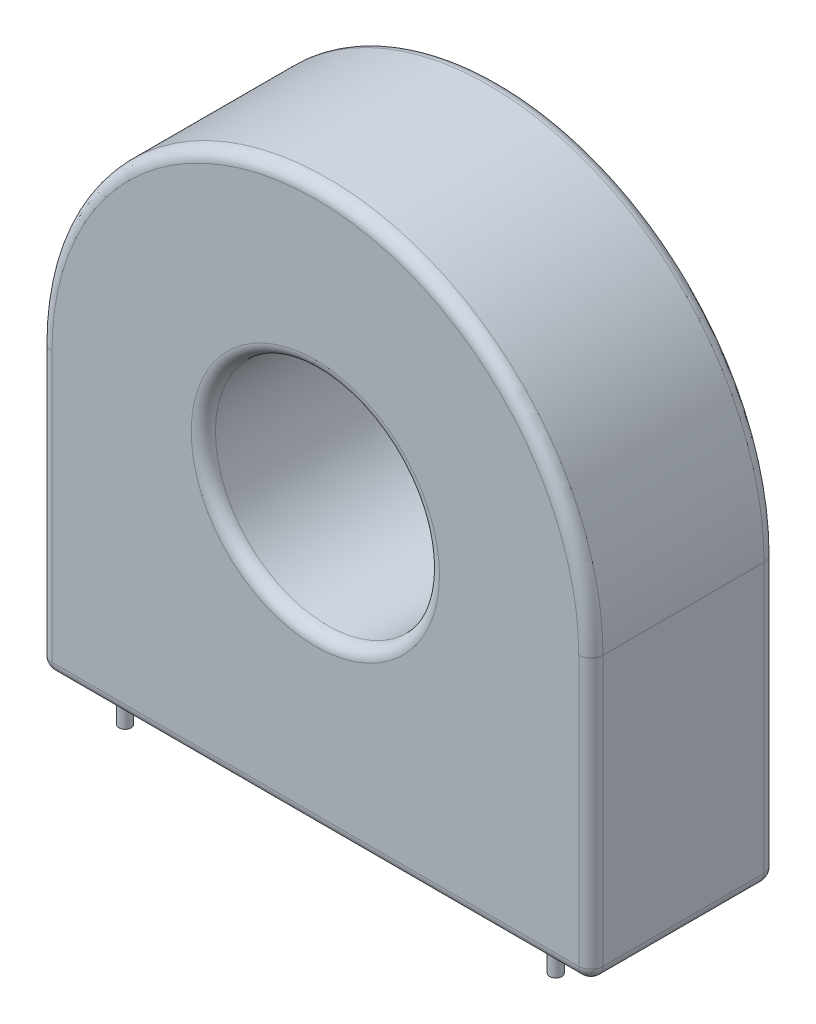
SolidWorks part; units mm, degrees
ref_plane "Front Plane" through (0, 0, 0) normal (0, 0, 1) x (1, 0, 0)
ref_plane "Top Plane" through (0, 0, 0) normal (0, 1, 0) x (1, 0, 0)
ref_plane "Right Plane" through (0, 0, 0) normal (1, 0, 0) x (0, 0, -1)
sketch "Sketch1" plane through (0, 0, 0) normal (0, 0, 1) x (1, 0, 0)
  line L0 (0, 56.047) -> (0, -94.9477) construction
  line L1 (0, 34.375) -> (50.579, 34.375) construction
  line L2 (-22.75, 11.625) -> (22.75, 11.625) construction
  line L3 (-22.75, 11.625) -> (-22.75, -11.625)
  line L4 (-22.75, -11.625) -> (22.75, -11.625)
  line L5 (22.75, 11.625) -> (22.75, -11.625)
  line L6 (-22.75, 11.625) -> (22.75, -11.625) construction
  line L7 (-22.75, -11.625) -> (22.75, 11.625) construction
  arc A0 (-22.75, 11.625) -> (22.75, 11.625) centre (0, 11.625) cw
  circle A1 centre (0, 11.625) radius 9.25
  point P2 (0, 0)
  dimension "D1" = 45.5
  dimension "D3" = 18.5
  dimension "D2" = 46
extrude "Boss-Extrude1" add sketch "Sketch1" along normal mid plane 15.3
sketch "Sketch2" plane through (0, -11.625, 0) normal (0, -1, 0) x (1, 0, 0)
  line L0 (0, 13.15) -> (0, 0) construction
  line L1 (0, 0) -> (25.5661, 0) construction
  line L2 (17.78, 5.58) -> (28.4302, 5.58) construction
  line L3 (-22.75, 7.65) -> (22.75, 7.65) construction
  circle A0 centre (17.78, 5.58) radius 0.5
  circle A1 centre (0, -4.58) radius 0.5
  circle A2 centre (-17.78, 5.58) radius 0.5
  dimension "D1" = 10.16
  dimension "D4" = 1
  dimension "D2" = 17.78
  dimension "D3" = 2.07
extrude "Boss-Extrude2" add sketch "Sketch2" along normal mid plane 5
fillet "Fillet1" radius 1 11 edges at (-22.75, 0, -7.65) (0, 34.375, -7.65) (22.75, 0, 7.65) (-22.75, 0, 7.65) (-22.75, -11.625, 0) (22.75, -11.625, 0) (0, -11.625, -7.65) (0, -11.625, 7.65) (22.75, 0, -7.65) (0, 34.375, 7.65) (9.25, 11.625, 7.65)
sketch "Sketch3" plane through (0, 0, -7.65) normal (0, 0, 1) x (1, 0, 0)
  line L0 (-19.836, -3.856) -> (19.836, -3.856) construction
  line L1 (-19.836, -9.106) -> (19.836, -9.106) construction
  text T0 "THAI LIN " font "Xolonium" height 4
  text T1 "TL76-5-100" font "Xolonium" height 4
  point P2 (0, -3.856)
  dimension "D1" = 5.25
extrude "Cut-Extrude1" cut sketch "Sketch3" along normal blind 0.01
sketch "Sketch4" plane through (0, -11.625, 0) normal (0, -1, 0) x (1, 0, 0)
  line L0 (-20.7266, 3.7883) -> (20.0523, 3.7883) construction
  line L1 (-5.0577, -0.3768) -> (5.4385, -0.3768) construction
  text T0 " #2                              #1" font "Xolonium" height 3
  text T1 "#3" font "Xolonium" height 3
  point P5 (-20.7266, 4.899)
  point P6 (-20.7266, 3.7883)
  point P7 (-4.304, -0.6545)
  point P8 (-5.0577, -0.3768)
  point P10 (0.1904, -0.3768)
extrude "Cut-Extrude2" cut sketch "Sketch4" against normal blind 0.01
